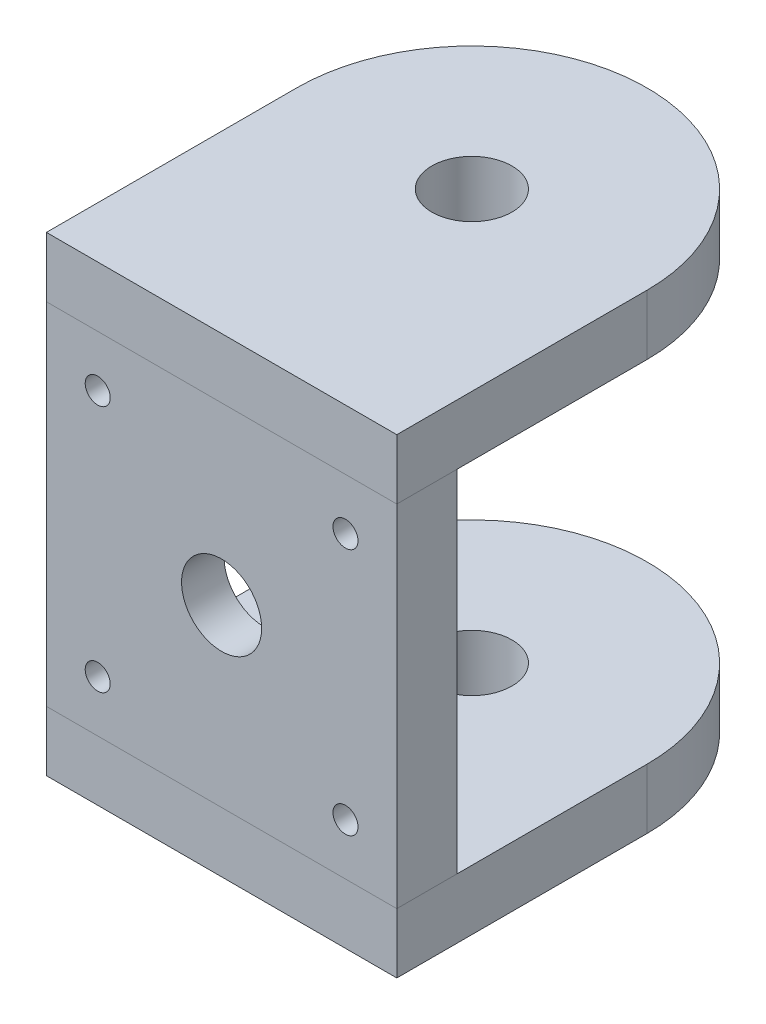
SolidWorks part; units mm, degrees
material "6061 Alloy"
ref_plane "Front Plane" through (0, 0, 0) normal (1, 0, 0) x (0, 1, 0)
ref_plane "Top Plane" through (0, 0, 0) normal (0, 0, 1) x (0, 1, 0)
ref_plane "Right Plane" through (0, 0, 0) normal (0, 1, 0) x (-1, 0, 0)
sketch "Sketch1" plane through (0, 0, 0) normal (0, 0, 1) x (0, 1, 0)
  line L1 (-35, -35) -> (35, -35)
  line L2 (-35, -35) -> (-35, 35)
  line L3 (-35, 35) -> (35, 35)
  line L4 (35, -35) -> (35, 35)
  line L5 (-35, -35) -> (35, 35) construction
  line L6 (-35, 35) -> (35, -35) construction
  circle A0 centre (0, 0) radius 25
  circle A1 centre (0, 0) radius 35 construction
  circle A2 centre (0, 0) radius 8
  circle A3 centre (-24.7487, 24.7487) radius 2.5
  circle A4 centre (24.7487, 24.7487) radius 2.5
  circle A5 centre (24.7487, -24.7487) radius 2.5
  circle A6 centre (-24.7487, -24.7487) radius 2.5
  point P0 (0, 0)
  point P21 (0, 0)
  dimension "D2" = 50
  dimension "D3" = 16
  dimension "D4" = 5
  dimension "D1" = 70
  dimension "D5" = 4
extrude "Boss-Extrude2" add sketch "Sketch1" along normal blind 12 contours L1 L4 L3 L2 A6 A5 A4 A3 A0 | A0 A2 region at (0, -34.0101, 0) region at (0, -24.2929, 0)
extrude "Cut-Extrude2" cut sketch "Sketch1<5>" along normal blind 3.5 contours A0
sketch "Sketch1<5>" plane through (0, 0, 0) normal (0, 0, 1) x (0, 1, 0) same geometry as "Sketch1"
sketch "Sketch2" plane through (0, 35, 0) normal (0, 1, 0) x (-1, 0, 0)
  line L0 (-35, 6) -> (35, 6) construction
  line L1 (-35, 12) -> (-35, 0) construction
  line L2 (35, 12) -> (35, 0) construction
  line L3 (0, 6.6) -> (0, -6.6) construction
  circle A0 centre (0, 6) radius 2.75
  circle A1 centre (18, 6) radius 2.75
  circle A2 centre (-18, 6) radius 2.75
  dimension "D1" = 5.5
  dimension "D2" = 2
extrude "Cut-Extrude3" cut sketch "Sketch2" against normal blind 8
sketch "Sketch3" plane through (0, 35, 0) normal (0, 1, 0) x (-1, 0, 0)
  line L1 (-35, 12) -> (35, 12)
  line L2 (-35, 12) -> (-35, -88)
  line L3 (-35, -88) -> (35, -88)
  line L4 (35, 12) -> (35, -88)
  line L5 (-35, 12) -> (35, -88) construction
  line L6 (-35, -88) -> (35, 12) construction
  point P4 (0, -38)
  dimension "D1" = 100
extrude "Boss-Extrude3" add sketch "Sketch3" along normal blind 12 separate body
mirror "Mirror1" about plane through (0, 0, 0) normal (0, 1, 0) of bodies 106
mirror "Mirror2" about plane through (0, 0, 0) normal (0, 1, 0) of "Cut-Extrude3"
sketch "Sketch4" plane through (0, -35, 0) normal (0, 1, 0) x (-1, 0, 0)
  circle A2 centre (-18, 6) radius 3.25
  circle A3 centre (-18, 6) radius 3.25
  circle A7 centre (0, 6) radius 3.25
  circle A8 centre (0, 6) radius 3.25
  circle A10 centre (18, 6) radius 3.25
  circle A11 centre (18, 6) radius 3.25
  dimension "D2" = 0.5
  dimension "D3" = 0.5
  dimension "D4" = 0.5
sketch "Sketch5" plane through (0, 47, 0) normal (0, 1, 0) x (-1, 0, 0)
  line L0 (0, 51.7) -> (0, -51.7) construction
  line L1 (-35, -88) -> (35, -88) construction
  circle A0 centre (0, -38) radius 8
  dimension "D1" = 16
  dimension "D2" = 50
extrude "Cut-Extrude4" cut sketch "Sketch5" against normal through all both and the other way through all
sketch "Sketch6" plane through (0, 47, 0) normal (0, 1, 0) x (-1, 0, 0)
  line L0 (-35, -38) -> (-35, -88)
  line L1 (-35, -88) -> (35, -88)
  line L2 (35, -88) -> (35, -38)
  arc A0 (-35, -38) -> (35, -38) centre (0, -38) ccw
extrude "Cut-Extrude5" cut sketch "Sketch6" against normal through all both and the other way through all
